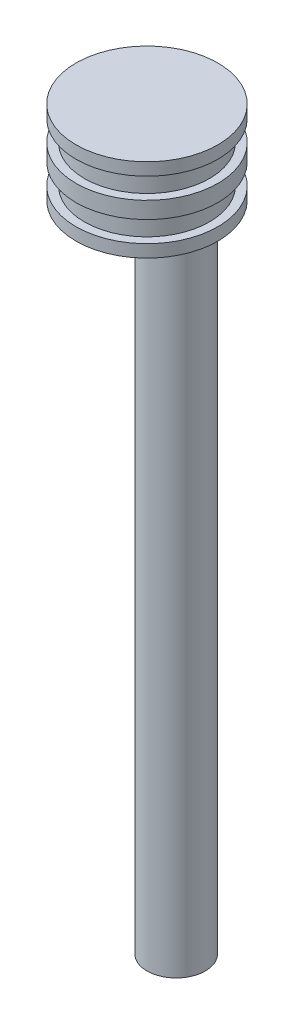
SolidWorks part; units mm, degrees
note: The reader was unsure of these and kept them because the rebuilt part matched: shared geometry of "Sketch2<2>", "Sketch2<3>".
ref_plane "Front Plane" through (0, 0, 0) normal (0, 0, 1) x (1, 0, 0)
ref_plane "Top Plane" through (0, 0, 0) normal (0, 1, 0) x (1, 0, 0)
ref_plane "Right Plane" through (0, 0, 0) normal (1, 0, 0) x (0, 0, -1)
sketch "Sketch2" plane through (0, 0, 0) normal (0, 1, 0) x (1, 0, 0)
  circle A0 centre (0, 0) radius 8.5
  dimension "D1" = 17
extrude "Boss-Extrude1" add sketch "Sketch2" along normal blind 10
extrude "Cut-Extrude1" cut sketch "Sketch2<2>" along normal blind 2.5 from offset 1.5
sketch "Sketch2<2>" plane through (0, 0, 0) normal (0, 1, 0) x (1, 0, 0) same geometry as "Sketch2"
extrude "Cut-Extrude2" cut sketch "Sketch2<3>" along normal blind 2.5 from offset 6
sketch "Sketch2<3>" plane through (0, 0, 0) normal (0, 1, 0) x (1, 0, 0) same geometry as "Sketch2"
sketch "Sketch4" plane through (0, 0, 0) normal (0, 1, 0) x (1, 0, 0)
  circle A0 centre (0, 0) radius 7.5
  dimension "D1" = 15
extrude "Boss-Extrude3" add sketch "Sketch4" along normal blind 9
sketch "Sketch5" plane through (0, 0, 0) normal (0, -1, 0) x (1, 0, 0)
  circle A0 centre (0, -3.5) radius 3.5
  dimension "D1" = 7
  dimension "D2" = 3.5
extrude "Boss-Extrude4" add sketch "Sketch5" along normal blind 80
